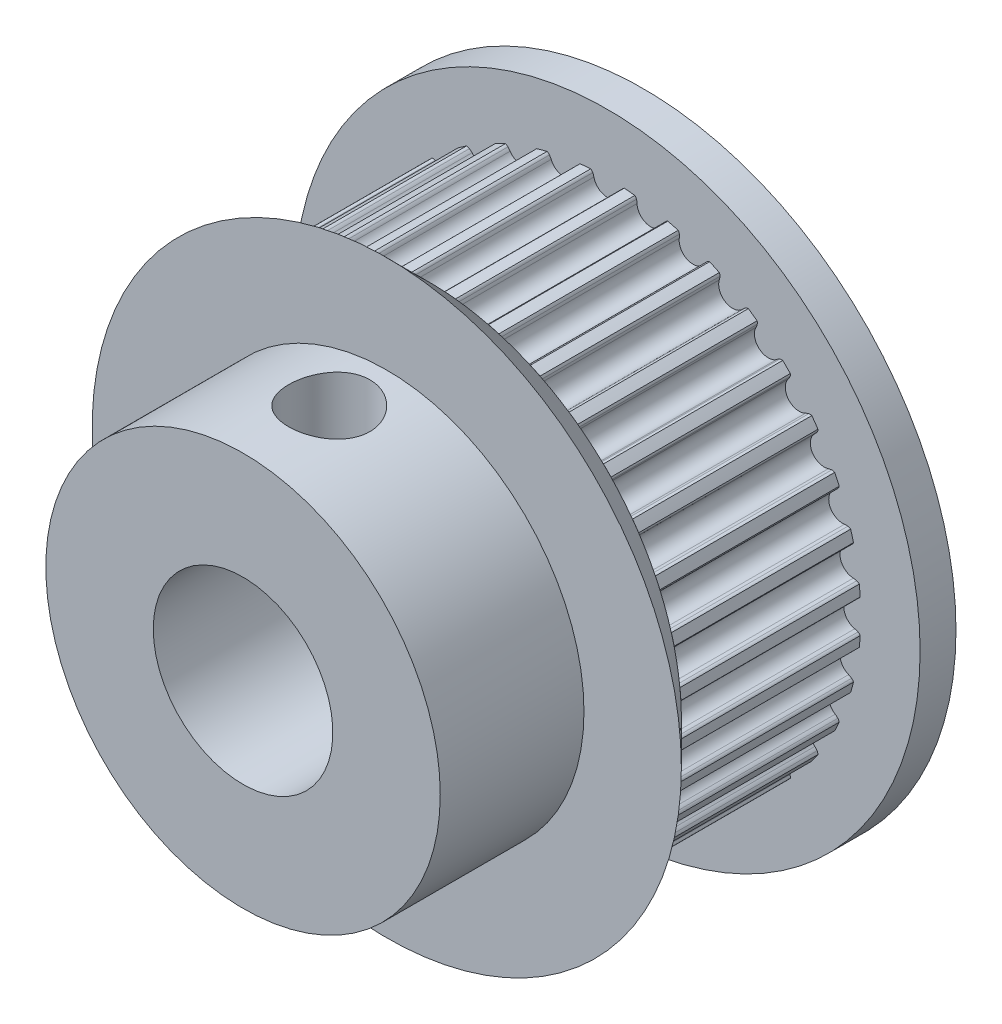
SolidWorks part; units mm, degrees
material "ABS"
ref_plane "Front Plane" through (0, 0, 0) normal (0, 0, 1) x (1, 0, 0)
ref_plane "Top Plane" through (0, 0, 0) normal (0, 1, 0) x (1, 0, 0)
ref_plane "Right Plane" through (0, 0, 0) normal (1, 0, 0) x (0, 0, -1)
sketch "Sketch1" plane through (0, 0, 0) normal (0, 1, 0) x (1, 0, 0)
  line L0 (11.21, -3.9687) -> (0, -3.9687)
  line L1 (0, -3.9687) -> (0, -5.8011)
  line L2 (0, -5.8011) -> (13.0424, -5.8011)
  line L4 (0, -3.9687) -> (0, -5.8011) construction
  line L5 (13.0424, -5.8011) -> (11.21, -3.9687)
  dimension "D1" = 11.21
  dimension "D2" = 45
revolve "Revolve1" add sketch "Sketch1" angle 360 about L4 reverse direction yes
sketch "Sketch2" plane through (0, 0, 3.9687) normal (0, 0, -1) x (-1, 0, 0)
  arc A0 (-3.1309, 10.7682) -> (-2.6727, 10.891) centre (0, 0) cw
  arc A6 (-1.2134, 11.1483) -> (-0.7409, 11.1896) centre (0, 0) cw
  arc A7 (-4.5233, 10.2614) -> (-4.4045, 10.2) centre (-4.5654, 10.0341) cw
  arc A8 (-4.4045, 10.2) -> (-4.3083, 10.0819) centre (-4.8573, 9.7334) cw
  arc A9 (-4.3083, 10.0819) -> (-3.1801, 10.4925) centre (-3.7894, 10.4113) ccw
  arc A10 (-3.1801, 10.4925) -> (-3.1824, 10.6448) centre (-2.5356, 10.5784) cw
  arc A11 (-3.1824, 10.6448) -> (-3.1309, 10.7682) centre (-2.9525, 10.6212) cw
  arc A12 (-2.6727, 10.891) -> (-2.5663, 10.8099) centre (-2.7537, 10.6745) cw
  arc A13 (-2.5663, 10.8099) -> (-2.4922, 10.6768) centre (-3.0933, 10.429) cw
  arc A14 (-2.4922, 10.6768) -> (-1.3098, 10.8853) centre (-1.9239, 10.9112) ccw
  arc A15 (-1.3098, 10.8853) -> (-1.2856, 11.0357) centre (-0.6601, 10.858) cw
  arc A16 (-1.2856, 11.0357) -> (-1.2134, 11.1483) centre (-1.0633, 10.9725) cw
  arc A17 (-0.7409, 11.1896) -> (-0.6502, 11.0913) centre (-0.8582, 10.9905) cw
  arc A18 (-0.6502, 11.0913) -> (-0.6003, 10.9474) centre (-1.2354, 10.8077) cw
  arc A19 (-0.6003, 10.9474) -> (0.6003, 10.9474) centre (0, 11.0795) ccw
  arc A20 (0.6003, 10.9474) -> (0.6502, 11.0913) centre (1.2354, 10.8077) cw
  arc A21 (0.6502, 11.0913) -> (0.7409, 11.1896) centre (0.8582, 10.9905) cw
  arc A22 (1.2134, 11.1483) -> (1.2856, 11.0357) centre (1.0633, 10.9725) cw
  arc A23 (1.2856, 11.0357) -> (1.3098, 10.8853) centre (0.6601, 10.858) cw
  arc A24 (1.3098, 10.8853) -> (2.4922, 10.6768) centre (1.9239, 10.9112) ccw
  arc A25 (2.4922, 10.6768) -> (2.5663, 10.8099) centre (3.0933, 10.429) cw
  arc A26 (2.5663, 10.8099) -> (2.6727, 10.891) centre (2.7537, 10.6745) cw
  arc A27 (3.1309, 10.7682) -> (3.1824, 10.6448) centre (2.9525, 10.6212) cw
  arc A28 (3.1824, 10.6448) -> (3.1801, 10.4925) centre (2.5356, 10.5784) cw
  arc A29 (3.1801, 10.4925) -> (4.3083, 10.0819) centre (3.7894, 10.4113) ccw
  arc A30 (4.3083, 10.0819) -> (4.4045, 10.2) centre (4.8573, 9.7334) cw
  arc A31 (4.4045, 10.2) -> (4.5233, 10.2614) centre (4.5654, 10.0341) cw
  arc A32 (4.9532, 10.0609) -> (4.9825, 9.9305) centre (4.752, 9.9471) cw
  arc A33 (4.9825, 9.9305) -> (4.9538, 9.7809) centre (4.334, 9.9774) cw
  arc A34 (4.9538, 9.7809) -> (5.9936, 9.1806) centre (5.5397, 9.5951) ccw
  arc A35 (5.9936, 9.1806) -> (6.1088, 9.2802) centre (6.4737, 8.742) cw
  arc A36 (6.1088, 9.2802) -> (6.2364, 9.32) centre (6.2385, 9.0889) cw
  arc A37 (6.625, 9.048) -> (6.6312, 8.9144) centre (6.4071, 8.9709) cw
  arc A38 (6.6312, 8.9144) -> (6.577, 8.7721) centre (6.0007, 9.0732) cw
  arc A39 (6.577, 8.7721) -> (7.4967, 8.0003) centre (7.1218, 8.4874) ccw
  arc A40 (7.4967, 8.0003) -> (7.6275, 8.0784) centre (7.8934, 7.4851) cw
  arc A41 (7.6275, 8.0784) -> (7.7601, 8.0955) centre (7.722, 7.8675) cw
  arc A42 (8.0955, 7.7601) -> (8.0784, 7.6275) centre (7.8675, 7.722) cw
  arc A43 (8.0784, 7.6275) -> (8.0003, 7.4967) centre (7.4851, 7.8934) cw
  arc A44 (8.0003, 7.4967) -> (8.7721, 6.577) centre (8.4874, 7.1218) ccw
  arc A45 (8.7721, 6.577) -> (8.9144, 6.6312) centre (9.0732, 6.0007) cw
  arc A46 (8.9144, 6.6312) -> (9.048, 6.625) centre (8.9709, 6.4071) cw
  arc A47 (9.32, 6.2364) -> (9.2802, 6.1088) centre (9.0889, 6.2385) cw
  arc A48 (9.2802, 6.1088) -> (9.1806, 5.9936) centre (8.742, 6.4737) cw
  arc A49 (9.1806, 5.9936) -> (9.7809, 4.9538) centre (9.5951, 5.5397) ccw
  arc A50 (9.7809, 4.9538) -> (9.9305, 4.9825) centre (9.9774, 4.334) cw
  arc A51 (9.9305, 4.9825) -> (10.0609, 4.9532) centre (9.9471, 4.752) cw
  arc A52 (10.2614, 4.5233) -> (10.2, 4.4045) centre (10.0341, 4.5654) cw
  arc A53 (10.2, 4.4045) -> (10.0819, 4.3083) centre (9.7334, 4.8573) cw
  arc A54 (10.0819, 4.3083) -> (10.4925, 3.1801) centre (10.4113, 3.7894) ccw
  arc A55 (10.4925, 3.1801) -> (10.6448, 3.1824) centre (10.5784, 2.5356) cw
  arc A56 (10.6448, 3.1824) -> (10.7682, 3.1309) centre (10.6212, 2.9525) cw
  arc A57 (10.891, 2.6727) -> (10.8099, 2.5663) centre (10.6745, 2.7537) cw
  arc A58 (10.8099, 2.5663) -> (10.6768, 2.4922) centre (10.429, 3.0933) cw
  arc A59 (10.6768, 2.4922) -> (10.8853, 1.3098) centre (10.9112, 1.9239) ccw
  arc A60 (10.8853, 1.3098) -> (11.0357, 1.2856) centre (10.858, 0.6601) cw
  arc A61 (11.0357, 1.2856) -> (11.1483, 1.2134) centre (10.9725, 1.0633) cw
  arc A62 (11.1896, 0.7409) -> (11.0913, 0.6502) centre (10.9905, 0.8582) cw
  arc A63 (11.0913, 0.6502) -> (10.9474, 0.6003) centre (10.8077, 1.2354) cw
  arc A64 (10.9474, 0.6003) -> (10.9474, -0.6003) centre (11.0795, 0) ccw
  arc A65 (10.9474, -0.6003) -> (11.0913, -0.6502) centre (10.8077, -1.2354) cw
  arc A66 (11.0913, -0.6502) -> (11.1896, -0.7409) centre (10.9905, -0.8582) cw
  arc A67 (11.1483, -1.2134) -> (11.0357, -1.2856) centre (10.9725, -1.0633) cw
  arc A68 (11.0357, -1.2856) -> (10.8853, -1.3098) centre (10.858, -0.6601) cw
  arc A69 (10.8853, -1.3098) -> (10.6768, -2.4922) centre (10.9112, -1.9239) ccw
  arc A70 (10.6768, -2.4922) -> (10.8099, -2.5663) centre (10.429, -3.0933) cw
  arc A71 (10.8099, -2.5663) -> (10.891, -2.6727) centre (10.6745, -2.7537) cw
  arc A72 (10.7682, -3.1309) -> (10.6448, -3.1824) centre (10.6212, -2.9525) cw
  arc A73 (10.6448, -3.1824) -> (10.4925, -3.1801) centre (10.5784, -2.5356) cw
  arc A74 (10.4925, -3.1801) -> (10.0819, -4.3083) centre (10.4113, -3.7894) ccw
  arc A75 (10.0819, -4.3083) -> (10.2, -4.4045) centre (9.7334, -4.8573) cw
  arc A76 (10.2, -4.4045) -> (10.2614, -4.5233) centre (10.0341, -4.5654) cw
  arc A77 (10.0609, -4.9532) -> (9.9305, -4.9825) centre (9.9471, -4.752) cw
  arc A78 (9.9305, -4.9825) -> (9.7809, -4.9538) centre (9.9774, -4.334) cw
  arc A79 (9.7809, -4.9538) -> (9.1806, -5.9936) centre (9.5951, -5.5397) ccw
  arc A80 (9.1806, -5.9936) -> (9.2802, -6.1088) centre (8.742, -6.4737) cw
  arc A81 (9.2802, -6.1088) -> (9.32, -6.2364) centre (9.0889, -6.2385) cw
  arc A82 (9.048, -6.625) -> (8.9144, -6.6312) centre (8.9709, -6.4071) cw
  arc A83 (8.9144, -6.6312) -> (8.7721, -6.577) centre (9.0732, -6.0007) cw
  arc A84 (8.7721, -6.577) -> (8.0003, -7.4967) centre (8.4874, -7.1218) ccw
  arc A85 (8.0003, -7.4967) -> (8.0784, -7.6275) centre (7.4851, -7.8934) cw
  arc A86 (8.0784, -7.6275) -> (8.0955, -7.7601) centre (7.8675, -7.722) cw
  arc A87 (7.7601, -8.0955) -> (7.6275, -8.0784) centre (7.722, -7.8675) cw
  arc A88 (7.6275, -8.0784) -> (7.4967, -8.0003) centre (7.8934, -7.4851) cw
  arc A89 (7.4967, -8.0003) -> (6.577, -8.7721) centre (7.1218, -8.4874) ccw
  arc A90 (6.577, -8.7721) -> (6.6312, -8.9144) centre (6.0007, -9.0732) cw
  arc A91 (6.6312, -8.9144) -> (6.625, -9.048) centre (6.4071, -8.9709) cw
  arc A92 (6.2364, -9.32) -> (6.1088, -9.2802) centre (6.2385, -9.0889) cw
  arc A93 (6.1088, -9.2802) -> (5.9936, -9.1806) centre (6.4737, -8.742) cw
  arc A94 (5.9936, -9.1806) -> (4.9538, -9.7809) centre (5.5397, -9.5951) ccw
  arc A95 (4.9538, -9.7809) -> (4.9825, -9.9305) centre (4.334, -9.9774) cw
  arc A96 (4.9825, -9.9305) -> (4.9532, -10.0609) centre (4.752, -9.9471) cw
  arc A97 (4.5233, -10.2614) -> (4.4045, -10.2) centre (4.5654, -10.0341) cw
  arc A98 (4.4045, -10.2) -> (4.3083, -10.0819) centre (4.8573, -9.7334) cw
  arc A99 (4.3083, -10.0819) -> (3.1801, -10.4925) centre (3.7894, -10.4113) ccw
  arc A100 (3.1801, -10.4925) -> (3.1824, -10.6448) centre (2.5356, -10.5784) cw
  arc A101 (3.1824, -10.6448) -> (3.1309, -10.7682) centre (2.9525, -10.6212) cw
  arc A102 (2.6727, -10.891) -> (2.5663, -10.8099) centre (2.7537, -10.6745) cw
  arc A103 (2.5663, -10.8099) -> (2.4922, -10.6768) centre (3.0933, -10.429) cw
  arc A104 (2.4922, -10.6768) -> (1.3098, -10.8853) centre (1.9239, -10.9112) ccw
  arc A105 (1.3098, -10.8853) -> (1.2856, -11.0357) centre (0.6601, -10.858) cw
  arc A106 (1.2856, -11.0357) -> (1.2134, -11.1483) centre (1.0633, -10.9725) cw
  arc A107 (0.7409, -11.1896) -> (0.6502, -11.0913) centre (0.8582, -10.9905) cw
  arc A108 (0.6502, -11.0913) -> (0.6003, -10.9474) centre (1.2354, -10.8077) cw
  arc A109 (0.6003, -10.9474) -> (-0.6003, -10.9474) centre (0, -11.0795) ccw
  arc A110 (-0.6003, -10.9474) -> (-0.6502, -11.0913) centre (-1.2354, -10.8077) cw
  arc A111 (-0.6502, -11.0913) -> (-0.7409, -11.1896) centre (-0.8582, -10.9905) cw
  arc A112 (-1.2134, -11.1483) -> (-1.2856, -11.0357) centre (-1.0633, -10.9725) cw
  arc A113 (-1.2856, -11.0357) -> (-1.3098, -10.8853) centre (-0.6601, -10.858) cw
  arc A114 (-1.3098, -10.8853) -> (-2.4922, -10.6768) centre (-1.9239, -10.9112) ccw
  arc A115 (-2.4922, -10.6768) -> (-2.5663, -10.8099) centre (-3.0933, -10.429) cw
  arc A116 (-2.5663, -10.8099) -> (-2.6727, -10.891) centre (-2.7537, -10.6745) cw
  arc A117 (-3.1309, -10.7682) -> (-3.1824, -10.6448) centre (-2.9525, -10.6212) cw
  arc A118 (-3.1824, -10.6448) -> (-3.1801, -10.4925) centre (-2.5356, -10.5784) cw
  arc A119 (-3.1801, -10.4925) -> (-4.3083, -10.0819) centre (-3.7894, -10.4113) ccw
  arc A120 (-4.3083, -10.0819) -> (-4.4045, -10.2) centre (-4.8573, -9.7334) cw
  arc A121 (-4.4045, -10.2) -> (-4.5233, -10.2614) centre (-4.5654, -10.0341) cw
  arc A122 (-4.9532, -10.0609) -> (-4.9825, -9.9305) centre (-4.752, -9.9471) cw
  arc A123 (-4.9825, -9.9305) -> (-4.9538, -9.7809) centre (-4.334, -9.9774) cw
  arc A124 (-4.9538, -9.7809) -> (-5.9936, -9.1806) centre (-5.5397, -9.5951) ccw
  arc A125 (-5.9936, -9.1806) -> (-6.1088, -9.2802) centre (-6.4737, -8.742) cw
  arc A126 (-6.1088, -9.2802) -> (-6.2364, -9.32) centre (-6.2385, -9.0889) cw
  arc A127 (-6.625, -9.048) -> (-6.6312, -8.9144) centre (-6.4071, -8.9709) cw
  arc A128 (-6.6312, -8.9144) -> (-6.577, -8.7721) centre (-6.0007, -9.0732) cw
  arc A129 (-6.577, -8.7721) -> (-7.4967, -8.0003) centre (-7.1218, -8.4874) ccw
  arc A130 (-7.4967, -8.0003) -> (-7.6275, -8.0784) centre (-7.8934, -7.4851) cw
  arc A131 (-7.6275, -8.0784) -> (-7.7601, -8.0955) centre (-7.722, -7.8675) cw
  arc A132 (-8.0955, -7.7601) -> (-8.0784, -7.6275) centre (-7.8675, -7.722) cw
  arc A133 (-8.0784, -7.6275) -> (-8.0003, -7.4967) centre (-7.4851, -7.8934) cw
  arc A134 (-8.0003, -7.4967) -> (-8.7721, -6.577) centre (-8.4874, -7.1218) ccw
  arc A135 (-8.7721, -6.577) -> (-8.9144, -6.6312) centre (-9.0732, -6.0007) cw
  arc A136 (-8.9144, -6.6312) -> (-9.048, -6.625) centre (-8.9709, -6.4071) cw
  arc A137 (-9.32, -6.2364) -> (-9.2802, -6.1088) centre (-9.0889, -6.2385) cw
  arc A138 (-9.2802, -6.1088) -> (-9.1806, -5.9936) centre (-8.742, -6.4737) cw
  arc A139 (-9.1806, -5.9936) -> (-9.7809, -4.9538) centre (-9.5951, -5.5397) ccw
  arc A140 (-9.7809, -4.9538) -> (-9.9305, -4.9825) centre (-9.9774, -4.334) cw
  arc A141 (-9.9305, -4.9825) -> (-10.0609, -4.9532) centre (-9.9471, -4.752) cw
  arc A142 (-10.2614, -4.5233) -> (-10.2, -4.4045) centre (-10.0341, -4.5654) cw
  arc A143 (-10.2, -4.4045) -> (-10.0819, -4.3083) centre (-9.7334, -4.8573) cw
  arc A144 (-10.0819, -4.3083) -> (-10.4925, -3.1801) centre (-10.4113, -3.7894) ccw
  arc A145 (-10.4925, -3.1801) -> (-10.6448, -3.1824) centre (-10.5784, -2.5356) cw
  arc A146 (-10.6448, -3.1824) -> (-10.7682, -3.1309) centre (-10.6212, -2.9525) cw
  arc A147 (-10.891, -2.6727) -> (-10.8099, -2.5663) centre (-10.6745, -2.7537) cw
  arc A148 (-10.8099, -2.5663) -> (-10.6768, -2.4922) centre (-10.429, -3.0933) cw
  arc A149 (-10.6768, -2.4922) -> (-10.8853, -1.3098) centre (-10.9112, -1.9239) ccw
  arc A150 (-10.8853, -1.3098) -> (-11.0357, -1.2856) centre (-10.858, -0.6601) cw
  arc A151 (-11.0357, -1.2856) -> (-11.1483, -1.2134) centre (-10.9725, -1.0633) cw
  arc A152 (-11.1896, -0.7409) -> (-11.0913, -0.6502) centre (-10.9905, -0.8582) cw
  arc A153 (-11.0913, -0.6502) -> (-10.9474, -0.6003) centre (-10.8077, -1.2354) cw
  arc A154 (-10.9474, -0.6003) -> (-10.9474, 0.6003) centre (-11.0795, 0) ccw
  arc A155 (-10.9474, 0.6003) -> (-11.0913, 0.6502) centre (-10.8077, 1.2354) cw
  arc A156 (-11.0913, 0.6502) -> (-11.1896, 0.7409) centre (-10.9905, 0.8582) cw
  arc A157 (-11.1483, 1.2134) -> (-11.0357, 1.2856) centre (-10.9725, 1.0633) cw
  arc A158 (-11.0357, 1.2856) -> (-10.8853, 1.3098) centre (-10.858, 0.6601) cw
  arc A159 (-10.8853, 1.3098) -> (-10.6768, 2.4922) centre (-10.9112, 1.9239) ccw
  arc A160 (-10.6768, 2.4922) -> (-10.8099, 2.5663) centre (-10.429, 3.0933) cw
  arc A161 (-10.8099, 2.5663) -> (-10.891, 2.6727) centre (-10.6745, 2.7537) cw
  arc A162 (-10.7682, 3.1309) -> (-10.6448, 3.1824) centre (-10.6212, 2.9525) cw
  arc A163 (-10.6448, 3.1824) -> (-10.4925, 3.1801) centre (-10.5784, 2.5356) cw
  arc A164 (-10.4925, 3.1801) -> (-10.0819, 4.3083) centre (-10.4113, 3.7894) ccw
  arc A165 (-10.0819, 4.3083) -> (-10.2, 4.4045) centre (-9.7334, 4.8573) cw
  arc A166 (-10.2, 4.4045) -> (-10.2614, 4.5233) centre (-10.0341, 4.5654) cw
  arc A167 (-10.0609, 4.9532) -> (-9.9305, 4.9825) centre (-9.9471, 4.752) cw
  arc A168 (-9.9305, 4.9825) -> (-9.7809, 4.9538) centre (-9.9774, 4.334) cw
  arc A169 (-9.7809, 4.9538) -> (-9.1806, 5.9936) centre (-9.5951, 5.5397) ccw
  arc A170 (-9.1806, 5.9936) -> (-9.2802, 6.1088) centre (-8.742, 6.4737) cw
  arc A171 (-9.2802, 6.1088) -> (-9.32, 6.2364) centre (-9.0889, 6.2385) cw
  arc A172 (-9.048, 6.625) -> (-8.9144, 6.6312) centre (-8.9709, 6.4071) cw
  arc A173 (-8.9144, 6.6312) -> (-8.7721, 6.577) centre (-9.0732, 6.0007) cw
  arc A174 (-8.7721, 6.577) -> (-8.0003, 7.4967) centre (-8.4874, 7.1218) ccw
  arc A175 (-8.0003, 7.4967) -> (-8.0784, 7.6275) centre (-7.4851, 7.8934) cw
  arc A176 (-8.0784, 7.6275) -> (-8.0955, 7.7601) centre (-7.8675, 7.722) cw
  arc A177 (-7.7601, 8.0955) -> (-7.6275, 8.0784) centre (-7.722, 7.8675) cw
  arc A178 (-7.6275, 8.0784) -> (-7.4967, 8.0003) centre (-7.8934, 7.4851) cw
  arc A179 (-7.4967, 8.0003) -> (-6.577, 8.7721) centre (-7.1218, 8.4874) ccw
  arc A180 (-6.577, 8.7721) -> (-6.6312, 8.9144) centre (-6.0007, 9.0732) cw
  arc A181 (-6.6312, 8.9144) -> (-6.625, 9.048) centre (-6.4071, 8.9709) cw
  arc A182 (-6.2364, 9.32) -> (-6.1088, 9.2802) centre (-6.2385, 9.0889) cw
  arc A183 (-6.1088, 9.2802) -> (-5.9936, 9.1806) centre (-6.4737, 8.742) cw
  arc A184 (-5.9936, 9.1806) -> (-4.9538, 9.7809) centre (-5.5397, 9.5951) ccw
  arc A185 (-4.9538, 9.7809) -> (-4.9825, 9.9305) centre (-4.334, 9.9774) cw
  arc A186 (-4.9825, 9.9305) -> (-4.9532, 10.0609) centre (-4.752, 9.9471) cw
  arc A187 (0.7409, 11.1896) -> (1.2134, 11.1483) centre (0, 0) cw
  arc A188 (2.6727, 10.891) -> (3.1309, 10.7682) centre (0, 0) cw
  arc A189 (4.5233, 10.2614) -> (4.9532, 10.0609) centre (0, 0) cw
  arc A190 (6.2364, 9.32) -> (6.625, 9.048) centre (0, 0) cw
  arc A191 (7.7601, 8.0955) -> (8.0955, 7.7601) centre (0, 0) cw
  arc A192 (9.048, 6.625) -> (9.32, 6.2364) centre (0, 0) cw
  arc A193 (10.0609, 4.9532) -> (10.2614, 4.5233) centre (0, 0) cw
  arc A194 (10.7682, 3.1309) -> (10.891, 2.6727) centre (0, 0) cw
  arc A195 (11.1483, 1.2134) -> (11.1896, 0.7409) centre (0, 0) cw
  arc A196 (11.1896, -0.7409) -> (11.1483, -1.2134) centre (0, 0) cw
  arc A197 (10.891, -2.6727) -> (10.7682, -3.1309) centre (0, 0) cw
  arc A198 (10.2614, -4.5233) -> (10.0609, -4.9532) centre (0, 0) cw
  arc A199 (9.32, -6.2364) -> (9.048, -6.625) centre (0, 0) cw
  arc A200 (8.0955, -7.7601) -> (7.7601, -8.0955) centre (0, 0) cw
  arc A201 (6.625, -9.048) -> (6.2364, -9.32) centre (0, 0) cw
  arc A202 (4.9532, -10.0609) -> (4.5233, -10.2614) centre (0, 0) cw
  arc A203 (3.1309, -10.7682) -> (2.6727, -10.891) centre (0, 0) cw
  arc A204 (1.2134, -11.1483) -> (0.7409, -11.1896) centre (0, 0) cw
  arc A205 (-0.7409, -11.1896) -> (-1.2134, -11.1483) centre (0, 0) cw
  arc A206 (-2.6727, -10.891) -> (-3.1309, -10.7682) centre (0, 0) cw
  arc A207 (-4.5233, -10.2614) -> (-4.9532, -10.0609) centre (0, 0) cw
  arc A208 (-6.2364, -9.32) -> (-6.625, -9.048) centre (0, 0) cw
  arc A209 (-7.7601, -8.0955) -> (-8.0955, -7.7601) centre (0, 0) cw
  arc A210 (-9.048, -6.625) -> (-9.32, -6.2364) centre (0, 0) cw
  arc A211 (-10.0609, -4.9532) -> (-10.2614, -4.5233) centre (0, 0) cw
  arc A212 (-10.7682, -3.1309) -> (-10.891, -2.6727) centre (0, 0) cw
  arc A213 (-11.1483, -1.2134) -> (-11.1896, -0.7409) centre (0, 0) cw
  arc A214 (-11.1896, 0.7409) -> (-11.1483, 1.2134) centre (0, 0) cw
  arc A215 (-10.891, 2.6727) -> (-10.7682, 3.1309) centre (0, 0) cw
  arc A216 (-10.2614, 4.5233) -> (-10.0609, 4.9532) centre (0, 0) cw
  arc A217 (-9.32, 6.2364) -> (-9.048, 6.625) centre (0, 0) cw
  arc A218 (-8.0955, 7.7601) -> (-7.7601, 8.0955) centre (0, 0) cw
  arc A219 (-6.625, 9.048) -> (-6.2364, 9.32) centre (0, 0) cw
  arc A220 (-4.9532, 10.0609) -> (-4.5233, 10.2614) centre (0, 0) cw
  point P410 (0, 0)
  dimension "D1" = 36
extrude "Boss-Extrude1" add sketch "Sketch2" along normal blind 7.9375
ref_plane "Plane1" through (0, 0, -3.9688) normal (0, 0, 1) x (1, 0, 0)
sketch "Sketch3" plane through (0, 0, -3.9688) normal (0, 0, 1) x (1, 0, 0)
  circle A0 centre (0, 0) radius 13.843
extrude "Boss-Extrude2" add sketch "Sketch3" against normal blind 1.5875
sketch "Sketch4" plane through (0, 0, 5.8011) normal (0, 0, 1) x (1, 0, 0)
  circle A0 centre (0, 0) radius 8.7312
extrude "Boss-Extrude3" add sketch "Sketch4" along normal blind 6.3627
hole_wizard "M7 Clearance Hole1" positions "Sketch6" profile "Sketch5" hole size "M7" standard "ANSI Metric"
sketch "Sketch6" plane through (0, 0, -5.5562) normal (0, 0, -1) x (-1, 0, 0)
  point P0 (0, 0)
sketch "Sketch5" plane through (0, 0, -5.5562) normal (1, 0, 0) x (0, 1, 0)
  line L0 (0, 0) -> (0, 17.7201)
  line L1 (0, 17.7201) -> (3.9751, 17.7201)
  line L2 (3.9751, 17.7201) -> (3.9751, 0)
  line L5 (3.9751, 0) -> (0, 0)
  line L11 (0, -6.35) -> (0, 107.95) construction
  dimension "Thru Hole Dia." = 7.9502
  dimension "Thru Hole Depth" = 17.7201
ref_plane "Plane2" through (0, 3.3858, 0) normal (0, -1, 0) x (-1, 0, 0)
hole_wizard "M3 Clearance Hole1" positions "Sketch8" profile "Sketch7" hole size "M3" standard "ANSI Metric" end condition through all
sketch "Sketch8" plane through (0, 3.3858, 0) normal (0, -1, 0) x (-1, 0, 0)
  point P0 (0, -8.3471)
sketch "Sketch7" plane through (0, 3.3858, 8.3471) normal (1, 0, 0) x (0, 0, -1)
  line L0 (0, 0) -> (0, 10.4572)
  line L1 (0, 10.4572) -> (1.8, 10.4572)
  line L2 (1.8, 10.4572) -> (1.8, 0)
  line L5 (1.8, 0) -> (0, 0)
  line L11 (0, -6.35) -> (0, 107.95) construction
  dimension "Thru Hole Dia." = 3.6
  dimension "Thru Hole Depth" = 10.4572
